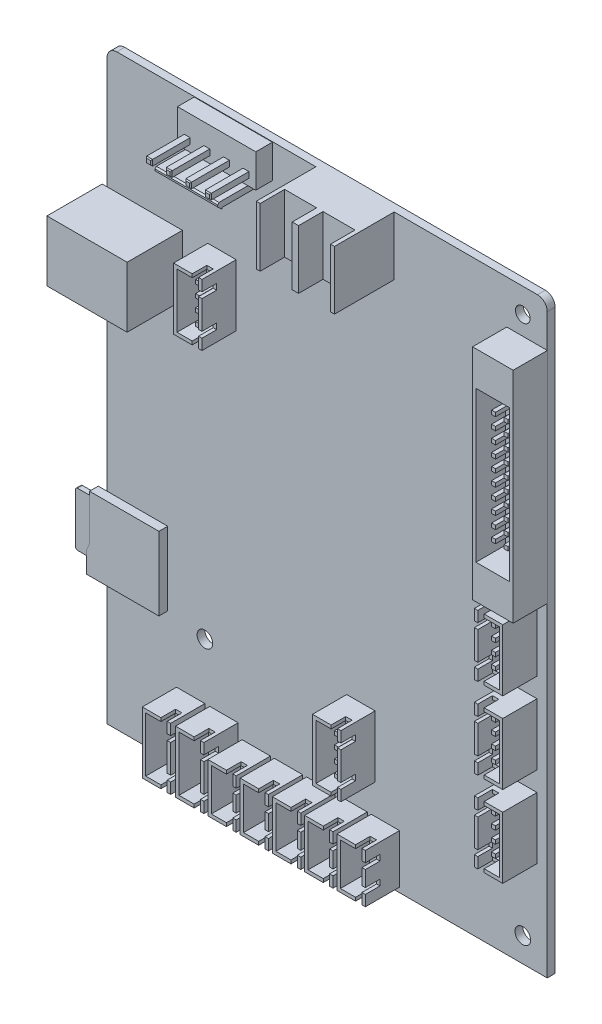
SolidWorks part; units mm, degrees
ref_plane "前视基准面" through (0, 0, 0) normal (0, 0, 1) x (1, 0, 0)
ref_plane "上视基准面" through (0, 0, 0) normal (0, 1, 0) x (1, 0, 0)
ref_plane "右视基准面" through (0, 0, 0) normal (1, 0, 0) x (0, 0, -1)
sketch "草图1" plane through (0, 0, 0) normal (0, 0, 1) x (1, 0, 0)
  line L0 (0, 0) -> (0, 50000) construction
  line L1 (43, -55) -> (-43, -55)
  line L2 (45, -53) -> (45, 53)
  line L3 (43, 55) -> (-43, 55)
  line L4 (-45, -53) -> (-45, 53)
  line L5 (45, -55) -> (-45, 55) construction
  line L6 (45, 55) -> (-45, -55) construction
  line L7 (0, 0) -> (50000, 0) construction
  arc A0 (-43, -55) -> (-45, -53) centre (-43, -53) cw
  arc A1 (43, -55) -> (45, -53) centre (43, -53) ccw
  arc A2 (45, 53) -> (43, 55) centre (43, 53) ccw
  arc A3 (-43, 55) -> (-45, 53) centre (-43, 53) ccw
  circle A4 centre (-40, 50) radius 1.5 construction
  circle A5 centre (40, 50) radius 1.5
  circle A6 centre (40, -50) radius 1.5 construction
  circle A7 centre (-40, -50) radius 1.5 construction
  point P0 (0, 0)
  dimension "D3" = 2
  dimension "D4" = 3
  dimension "D5" = 5
  dimension "D6" = 5
  dimension "D1" = 90
  dimension "D2" = 110
extrude "凸台-拉伸1" add sketch "草图1" along normal blind 1.6
sketch "草图2" plane through (0, 0, 1.6) normal (0, 0, 1) x (1, 0, 0)
  line L0 (43, 55) -> (-43, 55) construction
  line L1 (-46, 30.1) -> (-29.6, 30.1)
  line L2 (-46, 30.1) -> (-46, 17.7)
  line L3 (-46, 17.7) -> (-29.6, 17.7)
  line L4 (-29.6, 30.1) -> (-29.6, 17.7)
  line L5 (-45, 53) -> (-45, -53) construction
  dimension "D1" = 24.9
  dimension "D2" = 12.4
  dimension "D3" = 1
  dimension "D4" = 16.4
extrude "凸台-拉伸2" add sketch "草图2" along normal blind 11.3
sketch "草图3" plane through (-46, 0, 0) normal (-1, 0, 0) x (0, 0, 1)
  line L0 (12.9, 23.9) -> (50012.9, 23.9) construction
  line L1 (12.9, 30.1) -> (12.9, 17.7) construction
  line L2 (3, 28.7) -> (3, 19.1)
  line L3 (3, 19.1) -> (9.9, 19.1)
  line L4 (9.9, 19.1) -> (11.5, 20.7)
  line L5 (11.5, 20.7) -> (11.5, 27.1)
  line L6 (11.5, 27.1) -> (9.9, 28.7)
  line L7 (9.9, 28.7) -> (3, 28.7)
  line L8 (12.9, 30.1) -> (1.6, 30.1) construction
  line L9 (1.6, 30.1) -> (1.6, 17.7) construction
  line L11 (5.4, 26.6) -> (8.4, 26.6)
  line L12 (5.4, 26.6) -> (5.4, 21.2)
  line L13 (5.4, 21.2) -> (8.4, 21.2)
  line L14 (8.4, 26.6) -> (8.4, 21.2)
  point P4 (12.9, 23.9)
  dimension "D1" = 1.4
  dimension "D2" = 1.4
  dimension "D3" = 1.4
  dimension "D4" = 1.6
  dimension "D5" = 45
  dimension "D6" = 3
  dimension "D7" = 5.4
  dimension "D8" = 2.4
extrude "切除-拉伸1" cut sketch "草图3" against normal blind 9
sketch "草图4" plane through (0, 0, 1.6) normal (0, 0, 1) x (1, 0, 0)
  line L0 (-32.6, -23.8) -> (-32.6, -38.8)
  line L1 (-32.6, -38.8) -> (-47.4, -38.8)
  line L2 (-47.4, -38.8) -> (-47.4, -34.5)
  line L3 (-47.4, -34.5) -> (-46.8, -33.1886)
  line L4 (-46.8, -33.1886) -> (-46.8, -23.8)
  line L5 (-46.8, -23.8) -> (-32.6, -23.8)
  line L6 (-43, -55) -> (43, -55) construction
  line L7 (-45, 17.7) -> (-45, -53) construction
  dimension "D1" = 15
  dimension "D2" = 16.2
  dimension "D3" = 14.8
  dimension "D4" = 2.4
  dimension "D5" = 14.2
  dimension "D6" = 4.3
extrude "凸台-拉伸3" add sketch "草图4" along normal blind 1.8
sketch "草图5" plane through (-46.8, 0, 0) normal (-1, 0, 0) x (0, 0, 1)
  line L0 (3.4, -23.8) -> (3.4, -33.1886) construction
  line L1 (3.3, -24.6) -> (2.3, -24.6)
  line L2 (3.3, -24.6) -> (3.3, -35.6)
  line L3 (3.3, -35.6) -> (2.3, -35.6)
  line L4 (2.3, -24.6) -> (2.3, -35.6)
  line L5 (3.4, -23.8) -> (1.6, -23.8) construction
  dimension "D1" = 0.1
  dimension "D2" = 0.8
  dimension "D3" = 1
  dimension "D4" = 11
extrude "凸台-拉伸4" add sketch "草图5" along normal blind 3
fillet "圆角1" radius 0.5 2 edges at (-49.8, -24.6, 2.8) (-49.8, -35.6, 2.8)
sketch "草图6" plane through (0, 0, 1.6) normal (0, 0, 1) x (1, 0, 0)
  line L0 (-43, -55) -> (43, -55) construction
  line L1 (-25, -51.4) -> (-30.8, -51.4)
  line L2 (-25, -51.4) -> (-25, -64)
  line L3 (-25, -64) -> (-30.8, -64)
  line L4 (-30.8, -51.4) -> (-30.8, -64)
  line L5 (-45, -38.8) -> (-45, -53) construction
  dimension "D1" = 5.8
  dimension "D2" = 12.6
  dimension "D3" = 9
  dimension "D4" = 14.2
extrude "凸台-拉伸5" add sketch "草图6" along normal blind 7
sketch "草图7" plane through (0, 0, 8.6) normal (0, 0, 1) x (1, 0, 0)
  line L0 (-25, -51.4) -> (-30.8, -51.4) construction
  line L1 (-30.1, -52.1) -> (-25.7, -52.1)
  line L2 (-30.1, -52.1) -> (-30.1, -63.3)
  line L3 (-30.1, -63.3) -> (-25.7, -63.3)
  line L4 (-25.7, -52.1) -> (-25.7, -63.3)
  line L5 (-30.8, -64) -> (-25, -64) construction
  line L6 (-30.8, -51.4) -> (-30.8, -64) construction
  line L7 (-25, -64) -> (-25, -51.4) construction
  dimension "D1" = 0.7
  dimension "D2" = 0.7
  dimension "D3" = 0.7
  dimension "D4" = 0.7
extrude "切除-拉伸2" cut sketch "草图7" against normal blind 6
sketch "草图8" plane through (0, 0, 8.6) normal (0, 0, 1) x (1, 0, 0)
  line L1 (-27, -51.4) -> (-25.7, -51.4)
  line L2 (-27, -51.4) -> (-27, -52.1)
  line L3 (-27, -52.1) -> (-25.7, -52.1)
  line L4 (-25.7, -51.4) -> (-25.7, -52.1)
  line L5 (-25.7, -52.1) -> (-30.1, -52.1) construction
  line L7 (-25, -61.8) -> (-25, -60.6)
  line L8 (-25.7, -60.6) -> (-25, -60.6)
  line L9 (-25.7, -61.8) -> (-25.7, -60.6)
  line L10 (-25.7, -61.8) -> (-25, -61.8)
  line L12 (-25.7, -63.3) -> (-25.7, -52.1) construction
  line L13 (-25.7, -53.6) -> (-25, -53.6)
  line L14 (-25.7, -53.6) -> (-25.7, -54.8)
  line L15 (-25.7, -54.8) -> (-25, -54.8)
  line L16 (-25, -53.6) -> (-25, -54.8)
  line L17 (-25, -55) -> (-25, -51.4) construction
  line L19 (-25.7, -64) -> (-25.7, -63.3)
  line L20 (-27, -63.3) -> (-25.7, -63.3)
  line L21 (-27, -64) -> (-27, -63.3)
  line L22 (-27, -64) -> (-25.7, -64)
  line L23 (-30.8, -57.7) -> (49969.2, -57.7) construction
  line L24 (-30.8, -51.4) -> (-30.8, -64) construction
  line L26 (-30.8, -51.4) -> (-30.8, -55) construction
  line L27 (-25, -51.4) -> (-30.8, -51.4) construction
  point P34 (-30.8, -57.7)
  dimension "D1" = 3.8
  dimension "D2" = 2.2
  dimension "D4" = 1.2
extrude "切除-拉伸3" cut sketch "草图8" against normal blind 3
sketch "草图9" plane through (0, 0, 2.6) normal (0, 0, 1) x (1, 0, 0)
  line L0 (-30.8, -53.2) -> (49969.2, -53.2) construction
  line L1 (-30.8, -51.4) -> (-30.8, -55) construction
  line L2 (-27, -45.785) -> (-27, 49954.215) construction
  line L3 (-25, -55) -> (-25, -51.4) construction
  line L4 (-27, -51.55) -> (-27, -52.35)
  line L5 (-27, -49.05) -> (-27.8, -49.05)
  line L6 (-27, -49.05) -> (-27, -49.85)
  line L7 (-27, -49.85) -> (-27.8, -49.85)
  line L8 (-27.8, -49.05) -> (-27.8, -49.85)
  line L9 (-27, -51.55) -> (-27.8, -51.55)
  line L10 (-27.8, -51.55) -> (-27.8, -52.35)
  line L11 (-27, -52.35) -> (-27.8, -52.35)
  line L12 (-27, -54.05) -> (-27, -54.85)
  line L13 (-27, -54.05) -> (-27.8, -54.05)
  line L14 (-27.8, -54.05) -> (-27.8, -54.85)
  line L15 (-27, -54.85) -> (-27.8, -54.85)
  line L16 (-27, -56.55) -> (-27, -57.35)
  line L17 (-27, -56.55) -> (-27.8, -56.55)
  line L18 (-27.8, -56.55) -> (-27.8, -57.35)
  line L19 (-27, -57.35) -> (-27.8, -57.35)
  line L20 (-27, -49.05) -> (-27, -51.55) construction
  point P4 (-30.8, -53.2)
  dimension "D1" = 2
  dimension "D2" = 0.8
  dimension "D3" = 0.8
  dimension "D5" = 2.5
  dimension "D4" = 4
extrude "凸台-拉伸6" [suppressed] add sketch "草图9" along normal blind 4.5 and the other way blind 4
pattern_linear "阵列(线性)1" count 2 spacing 6.8 along (1, 0, 0) of "凸台-拉伸5", "切除-拉伸2", "切除-拉伸3", "凸台-拉伸6"
sketch "草图11" plane through (33.8907, 27.4604, 1.6) normal (0, 0, 1) x (1, 0, 0)
  line L1 (-24.0907, -62.7604) -> (-29.8907, -62.7604)
  line L2 (-24.0907, -62.7604) -> (-24.0907, -75.3604)
  line L3 (-24.0907, -75.3604) -> (-29.8907, -75.3604)
  line L4 (-29.8907, -62.7604) -> (-29.8907, -75.3604)
  line L6 (11.1093, -80.4604) -> (11.1093, 25.5396) construction
  line L7 (-76.8907, -82.4604) -> (-64.6907, -82.4604) construction
  dimension "D1" = 5.8
  dimension "D2" = 12.6
  dimension "D3" = 41
  dimension "D4" = 7.1
extrude "凸台-拉伸7" add sketch "草图11" along normal blind 7
sketch "草图13" plane through (33.8907, 27.4604, 8.6) normal (0, 0, 1) x (1, 0, 0)
  line L0 (-24.0907, -62.7604) -> (-29.8907, -62.7604) construction
  line L1 (-29.1907, -63.4604) -> (-24.7907, -63.4604)
  line L2 (-29.1907, -63.4604) -> (-29.1907, -74.6604)
  line L3 (-29.1907, -74.6604) -> (-24.7907, -74.6604)
  line L4 (-24.7907, -63.4604) -> (-24.7907, -74.6604)
  line L5 (-29.8907, -75.3604) -> (-24.0907, -75.3604) construction
  line L6 (-29.8907, -62.7604) -> (-29.8907, -75.3604) construction
  line L7 (-24.0907, -75.3604) -> (-24.0907, -62.7604) construction
  dimension "D1" = 0.7
  dimension "D2" = 0.7
  dimension "D3" = 0.7
  dimension "D4" = 0.7
extrude "切除-拉伸4" cut sketch "草图13" against normal blind 6
sketch "草图15" plane through (33.8907, 27.4604, 8.6) normal (0, 0, 1) x (1, 0, 0)
  line L1 (-26.0907, -62.7604) -> (-24.7907, -62.7604)
  line L2 (-26.0907, -62.7604) -> (-26.0907, -63.4604)
  line L3 (-26.0907, -63.4604) -> (-24.7907, -63.4604)
  line L4 (-24.7907, -62.7604) -> (-24.7907, -63.4604)
  line L5 (-24.7907, -63.4604) -> (-29.1907, -63.4604) construction
  line L7 (-24.0907, -73.1604) -> (-24.0907, -71.9604)
  line L8 (-24.7907, -71.9604) -> (-24.0907, -71.9604)
  line L9 (-24.7907, -73.1604) -> (-24.7907, -71.9604)
  line L10 (-24.7907, -73.1604) -> (-24.0907, -73.1604)
  line L12 (-24.7907, -74.6604) -> (-24.7907, -63.4604) construction
  line L13 (-24.7907, -64.9604) -> (-24.0907, -64.9604)
  line L14 (-24.7907, -64.9604) -> (-24.7907, -66.1604)
  line L15 (-24.7907, -66.1604) -> (-24.0907, -66.1604)
  line L16 (-24.0907, -64.9604) -> (-24.0907, -66.1604)
  line L17 (-24.0907, -75.3604) -> (-24.0907, -62.7604) construction
  line L19 (-24.7907, -75.3604) -> (-24.7907, -74.6604)
  line L20 (-26.0907, -74.6604) -> (-24.7907, -74.6604)
  line L21 (-26.0907, -75.3604) -> (-26.0907, -74.6604)
  line L22 (-26.0907, -75.3604) -> (-24.7907, -75.3604)
  line L23 (-30.8, -69.0604) -> (49969.2, -69.0604) construction
  line L24 (-29.8907, -62.7604) -> (-29.8907, -75.3604) construction
  line L26 (-29.8907, -62.7604) -> (-29.8907, -75.3604) construction
  line L27 (-24.0907, -62.7604) -> (-29.8907, -62.7604) construction
  point P34 (-29.8907, -69.0604)
  dimension "D1" = 3.8
  dimension "D2" = 2.2
  dimension "D4" = 1.2
extrude "切除-拉伸5" cut sketch "草图15" against normal blind 3
sketch "草图17" plane through (33.8907, 27.4604, 2.6) normal (0, 0, 1) x (1, 0, 0)
  line L0 (-30.8, -69.0604) -> (49969.2, -69.0604) construction
  line L1 (-29.8907, -62.7604) -> (-29.8907, -75.3604) construction
  line L2 (-26.0907, -45.785) -> (-26.0907, 49954.215) construction
  line L3 (-24.0907, -75.3604) -> (-24.0907, -62.7604) construction
  line L4 (-26.0907, -67.4104) -> (-26.0907, -68.2104)
  line L5 (-26.0907, -64.9104) -> (-26.8907, -64.9104)
  line L6 (-26.0907, -64.9104) -> (-26.0907, -65.7104)
  line L7 (-26.0907, -65.7104) -> (-26.8907, -65.7104)
  line L8 (-26.8907, -64.9104) -> (-26.8907, -65.7104)
  line L9 (-26.0907, -67.4104) -> (-26.8907, -67.4104)
  line L10 (-26.8907, -67.4104) -> (-26.8907, -68.2104)
  line L11 (-26.0907, -68.2104) -> (-26.8907, -68.2104)
  line L12 (-26.0907, -69.9104) -> (-26.0907, -70.7104)
  line L13 (-26.0907, -69.9104) -> (-26.8907, -69.9104)
  line L14 (-26.8907, -69.9104) -> (-26.8907, -70.7104)
  line L15 (-26.0907, -70.7104) -> (-26.8907, -70.7104)
  line L16 (-26.0907, -72.4104) -> (-26.0907, -73.2104)
  line L17 (-26.0907, -72.4104) -> (-26.8907, -72.4104)
  line L18 (-26.8907, -72.4104) -> (-26.8907, -73.2104)
  line L19 (-26.0907, -73.2104) -> (-26.8907, -73.2104)
  line L20 (-26.0907, -64.9104) -> (-26.0907, -67.4104) construction
  point P4 (-29.8907, -69.0604)
  dimension "D1" = 2
  dimension "D2" = 0.8
  dimension "D3" = 0.8
  dimension "D5" = 2.5
  dimension "D4" = 4
extrude "凸台-拉伸8" add sketch "草图17" along normal blind 4.5 and the other way blind 4
sketch "草图19" plane through (2.8423, 77.8774, 1.6) normal (0, 0, 1) x (1, 0, 0)
  line L0 (40.1577, -22.8774) -> (-45.8423, -22.8774) construction
  line L1 (-21.4423, -47.4774) -> (-27.2423, -47.4774)
  line L2 (-21.4423, -47.4774) -> (-21.4423, -60.0774)
  line L3 (-21.4423, -60.0774) -> (-27.2423, -60.0774)
  line L4 (-27.2423, -47.4774) -> (-27.2423, -60.0774)
  line L5 (-47.8423, -60.1774) -> (-47.8423, -101.6774) construction
  dimension "D1" = 5.8
  dimension "D2" = 12.6
  dimension "D3" = 24.6
  dimension "D4" = 20.6
extrude "凸台-拉伸9" add sketch "草图19" along normal blind 7
sketch "草图21" plane through (2.8423, 77.8774, 8.6) normal (0, 0, 1) x (1, 0, 0)
  line L0 (-21.4423, -47.4774) -> (-27.2423, -47.4774) construction
  line L1 (-26.5423, -48.1774) -> (-22.1423, -48.1774)
  line L2 (-26.5423, -48.1774) -> (-26.5423, -59.3774)
  line L3 (-26.5423, -59.3774) -> (-22.1423, -59.3774)
  line L4 (-22.1423, -48.1774) -> (-22.1423, -59.3774)
  line L5 (-27.2423, -60.0774) -> (-21.4423, -60.0774) construction
  line L6 (-27.2423, -47.4774) -> (-27.2423, -60.0774) construction
  line L7 (-21.4423, -60.0774) -> (-21.4423, -47.4774) construction
  dimension "D1" = 0.7
  dimension "D2" = 0.7
  dimension "D3" = 0.7
  dimension "D4" = 0.7
extrude "切除-拉伸6" cut sketch "草图21" against normal blind 6
sketch "草图23" plane through (2.8423, 77.8774, 8.6) normal (0, 0, 1) x (1, 0, 0)
  line L1 (-23.4423, -47.4774) -> (-22.1423, -47.4774)
  line L2 (-23.4423, -47.4774) -> (-23.4423, -48.1774)
  line L3 (-23.4423, -48.1774) -> (-22.1423, -48.1774)
  line L4 (-22.1423, -47.4774) -> (-22.1423, -48.1774)
  line L5 (-22.1423, -48.1774) -> (-26.5423, -48.1774) construction
  line L7 (-21.4423, -57.8774) -> (-21.4423, -56.6774)
  line L8 (-22.1423, -56.6774) -> (-21.4423, -56.6774)
  line L9 (-22.1423, -57.8774) -> (-22.1423, -56.6774)
  line L10 (-22.1423, -57.8774) -> (-21.4423, -57.8774)
  line L12 (-22.1423, -59.3774) -> (-22.1423, -48.1774) construction
  line L13 (-22.1423, -49.6774) -> (-21.4423, -49.6774)
  line L14 (-22.1423, -49.6774) -> (-22.1423, -50.8774)
  line L15 (-22.1423, -50.8774) -> (-21.4423, -50.8774)
  line L16 (-21.4423, -49.6774) -> (-21.4423, -50.8774)
  line L17 (-21.4423, -60.0774) -> (-21.4423, -47.4774) construction
  line L19 (-22.1423, -60.0774) -> (-22.1423, -59.3774)
  line L20 (-23.4423, -59.3774) -> (-22.1423, -59.3774)
  line L21 (-23.4423, -60.0774) -> (-23.4423, -59.3774)
  line L22 (-23.4423, -60.0774) -> (-22.1423, -60.0774)
  line L23 (-30.8, -53.7774) -> (49969.2, -53.7774) construction
  line L24 (-27.2423, -47.4774) -> (-27.2423, -60.0774) construction
  line L26 (-27.2423, -47.4774) -> (-27.2423, -60.0774) construction
  line L27 (-21.4423, -47.4774) -> (-27.2423, -47.4774) construction
  point P34 (-27.2423, -53.7774)
  dimension "D1" = 3.8
  dimension "D2" = 2.2
  dimension "D4" = 1.2
extrude "切除-拉伸7" cut sketch "草图23" against normal blind 3
sketch "草图25" plane through (2.8423, 77.8774, 2.6) normal (0, 0, 1) x (1, 0, 0)
  line L0 (-30.8, -53.7774) -> (49969.2, -53.7774) construction
  line L1 (-27.2423, -47.4774) -> (-27.2423, -60.0774) construction
  line L2 (-23.4423, -45.785) -> (-23.4423, 49954.215) construction
  line L3 (-21.4423, -60.0774) -> (-21.4423, -47.4774) construction
  line L4 (-23.4423, -52.1274) -> (-23.4423, -52.9274)
  line L5 (-23.4423, -49.6274) -> (-24.2423, -49.6274)
  line L6 (-23.4423, -49.6274) -> (-23.4423, -50.4274)
  line L7 (-23.4423, -50.4274) -> (-24.2423, -50.4274)
  line L8 (-24.2423, -49.6274) -> (-24.2423, -50.4274)
  line L9 (-23.4423, -52.1274) -> (-24.2423, -52.1274)
  line L10 (-24.2423, -52.1274) -> (-24.2423, -52.9274)
  line L11 (-23.4423, -52.9274) -> (-24.2423, -52.9274)
  line L12 (-23.4423, -54.6274) -> (-23.4423, -55.4274)
  line L13 (-23.4423, -54.6274) -> (-24.2423, -54.6274)
  line L14 (-24.2423, -54.6274) -> (-24.2423, -55.4274)
  line L15 (-23.4423, -55.4274) -> (-24.2423, -55.4274)
  line L16 (-23.4423, -57.1274) -> (-23.4423, -57.9274)
  line L17 (-23.4423, -57.1274) -> (-24.2423, -57.1274)
  line L18 (-24.2423, -57.1274) -> (-24.2423, -57.9274)
  line L19 (-23.4423, -57.9274) -> (-24.2423, -57.9274)
  line L20 (-23.4423, -49.6274) -> (-23.4423, -52.1274) construction
  point P4 (-27.2423, -53.7774)
  dimension "D1" = 2
  dimension "D2" = 0.8
  dimension "D3" = 0.8
  dimension "D5" = 2.5
  dimension "D4" = 4
extrude "凸台-拉伸10" add sketch "草图25" along normal blind 4.5 and the other way blind 4
sketch "草图27" plane through (67.7702, 21.0857, 1.6) normal (0, 0, 1) x (1, 0, 0)
  line L0 (-22.7702, -74.0857) -> (-22.7702, 31.9143) construction
  line L1 (-30.6702, -66.8857) -> (-24.8702, -66.8857)
  line L2 (-30.6702, -66.8857) -> (-30.6702, -54.2857)
  line L3 (-30.6702, -54.2857) -> (-24.8702, -54.2857)
  line L4 (-24.8702, -66.8857) -> (-24.8702, -54.2857)
  line L5 (-110.7702, -76.0857) -> (-98.5702, -76.0857) construction
  dimension "D1" = 5.8
  dimension "D2" = 12.6
  dimension "D3" = 2.1
  dimension "D4" = 9.2
extrude "凸台-拉伸11" add sketch "草图27" along normal blind 7
sketch "草图29" plane through (67.7702, 21.0857, 8.6) normal (0, 0, 1) x (1, 0, 0)
  line L0 (-30.6702, -66.8857) -> (-24.8702, -66.8857) construction
  line L1 (-25.5702, -66.1857) -> (-29.9702, -66.1857)
  line L2 (-25.5702, -66.1857) -> (-25.5702, -54.9857)
  line L3 (-25.5702, -54.9857) -> (-29.9702, -54.9857)
  line L4 (-29.9702, -66.1857) -> (-29.9702, -54.9857)
  line L5 (-24.8702, -54.2857) -> (-30.6702, -54.2857) construction
  line L6 (-24.8702, -66.8857) -> (-24.8702, -54.2857) construction
  line L7 (-30.6702, -54.2857) -> (-30.6702, -66.8857) construction
  dimension "D1" = 0.7
  dimension "D2" = 0.7
  dimension "D3" = 0.7
  dimension "D4" = 0.7
extrude "切除-拉伸8" cut sketch "草图29" against normal blind 6
sketch "草图31" plane through (67.7702, 21.0857, 8.6) normal (0, 0, 1) x (1, 0, 0)
  line L1 (-28.6702, -66.8857) -> (-29.9702, -66.8857)
  line L2 (-28.6702, -66.8857) -> (-28.6702, -66.1857)
  line L3 (-28.6702, -66.1857) -> (-29.9702, -66.1857)
  line L4 (-29.9702, -66.8857) -> (-29.9702, -66.1857)
  line L5 (-29.9702, -66.1857) -> (-25.5702, -66.1857) construction
  line L7 (-30.6702, -56.4857) -> (-30.6702, -57.6857)
  line L8 (-29.9702, -57.6857) -> (-30.6702, -57.6857)
  line L9 (-29.9702, -56.4857) -> (-29.9702, -57.6857)
  line L10 (-29.9702, -56.4857) -> (-30.6702, -56.4857)
  line L12 (-29.9702, -54.9857) -> (-29.9702, -66.1857) construction
  line L13 (-29.9702, -64.6857) -> (-30.6702, -64.6857)
  line L14 (-29.9702, -64.6857) -> (-29.9702, -63.4857)
  line L15 (-29.9702, -63.4857) -> (-30.6702, -63.4857)
  line L16 (-30.6702, -64.6857) -> (-30.6702, -63.4857)
  line L17 (-30.6702, -54.2857) -> (-30.6702, -66.8857) construction
  line L19 (-29.9702, -54.2857) -> (-29.9702, -54.9857)
  line L20 (-28.6702, -54.9857) -> (-29.9702, -54.9857)
  line L21 (-28.6702, -54.2857) -> (-28.6702, -54.9857)
  line L22 (-28.6702, -54.2857) -> (-29.9702, -54.2857)
  line L23 (-30.8, -60.5857) -> (49969.2, -60.5857) construction
  line L24 (-24.8702, -66.8857) -> (-24.8702, -54.2857) construction
  line L26 (-24.8702, -66.8857) -> (-24.8702, -54.2857) construction
  line L27 (-30.6702, -66.8857) -> (-24.8702, -66.8857) construction
  point P34 (-24.8702, -60.5857)
  dimension "D1" = 3.8
  dimension "D2" = 2.2
  dimension "D4" = 1.2
extrude "切除-拉伸9" cut sketch "草图31" against normal blind 3
sketch "草图33" plane through (67.7702, 21.0857, 2.6) normal (0, 0, 1) x (1, 0, 0)
  line L0 (-30.8, -60.5857) -> (49969.2, -60.5857) construction
  line L1 (-24.8702, -66.8857) -> (-24.8702, -54.2857) construction
  line L2 (-27.8702, -45.785) -> (-27.8702, 49954.215) construction
  line L3 (-30.6702, -54.2857) -> (-30.6702, -66.8857) construction
  line L4 (-27.8702, -58.9357) -> (-27.8702, -59.7357)
  line L5 (-27.8702, -56.4357) -> (-28.6702, -56.4357)
  line L6 (-27.8702, -56.4357) -> (-27.8702, -57.2357)
  line L7 (-27.8702, -57.2357) -> (-28.6702, -57.2357)
  line L8 (-28.6702, -56.4357) -> (-28.6702, -57.2357)
  line L9 (-27.8702, -58.9357) -> (-28.6702, -58.9357)
  line L10 (-28.6702, -58.9357) -> (-28.6702, -59.7357)
  line L11 (-27.8702, -59.7357) -> (-28.6702, -59.7357)
  line L12 (-27.8702, -61.4357) -> (-27.8702, -62.2357)
  line L13 (-27.8702, -61.4357) -> (-28.6702, -61.4357)
  line L14 (-28.6702, -61.4357) -> (-28.6702, -62.2357)
  line L15 (-27.8702, -62.2357) -> (-28.6702, -62.2357)
  line L16 (-27.8702, -63.9357) -> (-27.8702, -64.7357)
  line L17 (-27.8702, -63.9357) -> (-28.6702, -63.9357)
  line L18 (-28.6702, -63.9357) -> (-28.6702, -64.7357)
  line L19 (-27.8702, -64.7357) -> (-28.6702, -64.7357)
  line L20 (-27.8702, -56.4357) -> (-27.8702, -58.9357) construction
  point P4 (-24.8702, -60.5857)
  dimension "D1" = 2.8
  dimension "D2" = 0.8
  dimension "D3" = 0.8
  dimension "D5" = 2.5
  dimension "D4" = 4
extrude "凸台-拉伸12" add sketch "草图33" along normal blind 4.5 and the other way blind 4
pattern_linear "阵列(线性)2" count 3 spacing 16.6 along (0, 1, 0) of "凸台-拉伸11", "切除-拉伸8", "切除-拉伸9", "凸台-拉伸12"
sketch "草图35" plane through (13.4499, -1.0229, 1.6) normal (0, 0, 1) x (1, 0, 0)
  line L1 (-25.0499, -52.9771) -> (-30.8499, -52.9771)
  line L2 (-25.0499, -52.9771) -> (-25.0499, -62.9771)
  line L3 (-25.0499, -62.9771) -> (-30.8499, -62.9771)
  line L4 (-30.8499, -52.9771) -> (-30.8499, -62.9771)
  line L6 (-56.4499, -53.9771) -> (-44.2499, -53.9771) construction
  line L7 (-58.4499, -37.7771) -> (-58.4499, -51.9771) construction
  dimension "D1" = 5.8
  dimension "D2" = 10
  dimension "D3" = 9
  dimension "D4" = 27.6
extrude "凸台-拉伸13" add sketch "草图35" along normal blind 7
sketch "草图37" plane through (13.4499, -1.0229, 8.6) normal (0, 0, 1) x (1, 0, 0)
  line L0 (-25.0499, -52.9771) -> (-30.8499, -52.9771) construction
  line L1 (-30.1499, -53.6771) -> (-25.7499, -53.6771)
  line L2 (-30.1499, -53.6771) -> (-30.1499, -62.2771)
  line L3 (-30.1499, -62.2771) -> (-25.7499, -62.2771)
  line L4 (-25.7499, -53.6771) -> (-25.7499, -62.2771)
  line L5 (-30.8499, -62.9771) -> (-25.0499, -62.9771) construction
  line L6 (-30.8499, -52.9771) -> (-30.8499, -62.9771) construction
  line L7 (-25.0499, -62.9771) -> (-25.0499, -52.9771) construction
  dimension "D1" = 0.7
  dimension "D2" = 0.7
  dimension "D3" = 0.7
  dimension "D4" = 0.7
extrude "切除-拉伸10" cut sketch "草图37" against normal blind 6
sketch "草图39" plane through (13.4499, -1.0229, 8.6) normal (0, 0, 1) x (1, 0, 0)
  line L1 (-27.0499, -52.9771) -> (-25.7499, -52.9771)
  line L2 (-27.0499, -52.9771) -> (-27.0499, -53.6771)
  line L3 (-27.0499, -53.6771) -> (-25.7499, -53.6771)
  line L4 (-25.7499, -52.9771) -> (-25.7499, -53.6771)
  line L5 (-25.7499, -53.6771) -> (-30.1499, -53.6771) construction
  line L7 (-25.0499, -60.7771) -> (-25.0499, -59.5771)
  line L8 (-25.7499, -59.5771) -> (-25.0499, -59.5771)
  line L9 (-25.7499, -60.7771) -> (-25.7499, -59.5771)
  line L10 (-25.7499, -60.7771) -> (-25.0499, -60.7771)
  line L12 (-25.7499, -62.2771) -> (-25.7499, -53.6771) construction
  line L13 (-25.7499, -55.1771) -> (-25.0499, -55.1771)
  line L14 (-25.7499, -55.1771) -> (-25.7499, -56.3771)
  line L15 (-25.7499, -56.3771) -> (-25.0499, -56.3771)
  line L16 (-25.0499, -55.1771) -> (-25.0499, -56.3771)
  line L17 (-25.0499, -53.9771) -> (-25.0499, -52.9771) construction
  line L19 (-25.7499, -62.9771) -> (-25.7499, -62.2771)
  line L20 (-27.0499, -62.2771) -> (-25.7499, -62.2771)
  line L21 (-27.0499, -62.9771) -> (-27.0499, -62.2771)
  line L22 (-27.0499, -62.9771) -> (-25.7499, -62.9771)
  line L23 (-30.8, -57.9771) -> (49969.2, -57.9771) construction
  line L24 (-30.8499, -52.9771) -> (-30.8499, -62.9771) construction
  line L26 (-30.8499, -52.9771) -> (-30.8499, -53.9771) construction
  line L27 (-25.0499, -52.9771) -> (-30.8499, -52.9771) construction
  point P34 (-30.8499, -57.9771)
  dimension "D1" = 3.8
  dimension "D2" = 2.2
  dimension "D4" = 1.2
extrude "切除-拉伸11" cut sketch "草图39" against normal blind 3
sketch "草图41" plane through (13.4499, -1.0229, 2.6) normal (0, 0, 1) x (1, 0, 0)
  line L0 (-30.8, -53.4771) -> (49969.2, -53.4771) construction
  line L1 (-30.8499, -52.9771) -> (-30.8499, -53.9771) construction
  line L2 (-27.0499, -45.785) -> (-27.0499, 49954.215) construction
  line L3 (-25.0499, -53.9771) -> (-25.0499, -52.9771) construction
  line L4 (-27.0499, -53.0771) -> (-27.0499, -53.8771)
  line L5 (-27.0499, -50.5771) -> (-27.8499, -50.5771)
  line L6 (-27.0499, -50.5771) -> (-27.0499, -51.3771)
  line L7 (-27.0499, -51.3771) -> (-27.8499, -51.3771)
  line L8 (-27.8499, -50.5771) -> (-27.8499, -51.3771)
  line L9 (-27.0499, -53.0771) -> (-27.8499, -53.0771)
  line L10 (-27.8499, -53.0771) -> (-27.8499, -53.8771)
  line L11 (-27.0499, -53.8771) -> (-27.8499, -53.8771)
  line L12 (-27.0499, -55.5771) -> (-27.0499, -56.3771)
  line L13 (-27.0499, -55.5771) -> (-27.8499, -55.5771)
  line L14 (-27.8499, -55.5771) -> (-27.8499, -56.3771)
  line L15 (-27.0499, -56.3771) -> (-27.8499, -56.3771)
  line L20 (-27.0499, -50.5771) -> (-27.0499, -53.0771) construction
  line L21 (-27.0499, -58.0771) -> (-27.0499, -58.8771) [skipped]
  line L22 (-27.0499, -58.0771) -> (-27.8499, -58.0771) [skipped]
  line L23 (-27.8499, -58.0771) -> (-27.8499, -58.8771) [skipped]
  line L24 (-27.0499, -58.8771) -> (-27.8499, -58.8771) [skipped]
  point P4 (-30.8499, -53.4771)
  dimension "D1" = 2
  dimension "D2" = 0.8
  dimension "D3" = 0.8
  dimension "D5" = 2.5
  dimension "D4" = 4
extrude "凸台-拉伸14" [suppressed] add sketch "草图41" along normal blind 4.5 and the other way blind 4
pattern_linear "阵列(线性)3" count 5 spacing 6.6 along (1, 0, 0) of "凸台-拉伸13", "切除-拉伸10", "切除-拉伸11", "凸台-拉伸14"
sketch "草图43" plane through (66.8909, 85.5626, 1.6) normal (0, 0, 1) x (1, 0, 0)
  line L1 (-30.1665, -84.2273) -> (-21.8665, -84.2273)
  line L2 (-30.1665, -84.2273) -> (-30.1665, -39.4273)
  line L3 (-30.1665, -39.4273) -> (-21.8665, -39.4273)
  line L4 (-21.8665, -84.2273) -> (-21.8665, -39.4273)
  dimension "D1" = 8.3
  dimension "D2" = 44.8
extrude "凸台-拉伸15" add sketch "草图43" along normal blind 7
sketch "草图45" plane through (66.8909, 85.5626, 8.6) normal (0, 0, 1) x (1, 0, 0)
  line L0 (-30.1665, -84.2273) -> (-21.8665, -84.2273) construction
  line L1 (-22.5665, -77.2273) -> (-29.4665, -77.2273)
  line L2 (-22.5665, -77.2273) -> (-22.5665, -46.4273)
  line L3 (-22.5665, -46.4273) -> (-29.4665, -46.4273)
  line L4 (-29.4665, -77.2273) -> (-29.4665, -46.4273)
  line L5 (-21.8665, -39.4273) -> (-30.1665, -39.4273) construction
  line L6 (-21.8665, -84.2273) -> (-21.8665, -39.4273) construction
  line L7 (-30.1665, -39.4273) -> (-30.1665, -84.2273) construction
  dimension "D1" = 7
  dimension "D2" = 7
  dimension "D3" = 0.7
  dimension "D4" = 0.7
extrude "切除-拉伸12" cut sketch "草图45" against normal blind 6
sketch "草图49" plane through (66.8909, 85.5626, 2.6) normal (0, 0, 1) x (1, 0, 0)
  line L0 (-30.8, -61.8273) -> (49969.2, -61.8273) construction
  line L1 (-21.8665, -84.2273) -> (-21.8665, -39.4273) construction
  line L2 (-26.9665, -45.785) -> (-26.9665, 49954.215) construction
  line L3 (-30.1665, -39.4273) -> (-30.1665, -84.2273) construction
  line L4 (-26.9665, -52.6773) -> (-26.9665, -53.4773)
  line L5 (-26.9665, -50.1773) -> (-27.7665, -50.1773)
  line L6 (-26.9665, -50.1773) -> (-26.9665, -50.9773)
  line L7 (-26.9665, -50.9773) -> (-27.7665, -50.9773)
  line L8 (-27.7665, -50.1773) -> (-27.7665, -50.9773)
  line L9 (-26.9665, -52.6773) -> (-27.7665, -52.6773)
  line L10 (-27.7665, -52.6773) -> (-27.7665, -53.4773)
  line L11 (-26.9665, -53.4773) -> (-27.7665, -53.4773)
  line L12 (-26.9665, -55.1773) -> (-26.9665, -55.9773)
  line L13 (-26.9665, -55.1773) -> (-27.7665, -55.1773)
  line L14 (-27.7665, -55.1773) -> (-27.7665, -55.9773)
  line L15 (-26.9665, -55.9773) -> (-27.7665, -55.9773)
  line L16 (-26.9665, -57.6773) -> (-26.9665, -58.4773)
  line L17 (-26.9665, -57.6773) -> (-27.7665, -57.6773)
  line L18 (-27.7665, -57.6773) -> (-27.7665, -58.4773)
  line L19 (-26.9665, -58.4773) -> (-27.7665, -58.4773)
  line L20 (-26.9665, -50.1773) -> (-26.9665, -52.6773) construction
  line L21 (-26.9665, -60.1773) -> (-26.9665, -60.9773)
  line L22 (-26.9665, -60.1773) -> (-27.7665, -60.1773)
  line L23 (-27.7665, -60.1773) -> (-27.7665, -60.9773)
  line L24 (-26.9665, -60.9773) -> (-27.7665, -60.9773)
  line L25 (-26.9665, -62.6773) -> (-26.9665, -63.4773)
  line L26 (-26.9665, -62.6773) -> (-27.7665, -62.6773)
  line L27 (-27.7665, -62.6773) -> (-27.7665, -63.4773)
  line L28 (-26.9665, -63.4773) -> (-27.7665, -63.4773)
  line L29 (-26.9665, -65.1773) -> (-26.9665, -65.9773)
  line L30 (-26.9665, -65.1773) -> (-27.7665, -65.1773)
  line L31 (-27.7665, -65.1773) -> (-27.7665, -65.9773)
  line L32 (-26.9665, -65.9773) -> (-27.7665, -65.9773)
  line L33 (-26.9665, -67.6773) -> (-26.9665, -68.4773)
  line L34 (-26.9665, -67.6773) -> (-27.7665, -67.6773)
  line L35 (-27.7665, -67.6773) -> (-27.7665, -68.4773)
  line L36 (-26.9665, -68.4773) -> (-27.7665, -68.4773)
  line L37 (-26.9665, -70.1773) -> (-26.9665, -70.9773)
  line L38 (-26.9665, -70.1773) -> (-27.7665, -70.1773)
  line L39 (-27.7665, -70.1773) -> (-27.7665, -70.9773)
  line L40 (-26.9665, -70.9773) -> (-27.7665, -70.9773)
  line L41 (-26.9665, -72.6773) -> (-26.9665, -73.4773)
  line L42 (-26.9665, -72.6773) -> (-27.7665, -72.6773)
  line L43 (-27.7665, -72.6773) -> (-27.7665, -73.4773)
  line L44 (-26.9665, -73.4773) -> (-27.7665, -73.4773)
  line L45 (-24.4065, -52.6773) -> (-24.4065, -53.4773)
  line L46 (-24.4065, -50.1773) -> (-25.2065, -50.1773)
  line L47 (-24.4065, -50.1773) -> (-24.4065, -50.9773)
  line L48 (-24.4065, -50.9773) -> (-25.2065, -50.9773)
  line L49 (-25.2065, -50.1773) -> (-25.2065, -50.9773)
  line L50 (-24.4065, -52.6773) -> (-25.2065, -52.6773)
  line L51 (-25.2065, -52.6773) -> (-25.2065, -53.4773)
  line L52 (-24.4065, -53.4773) -> (-25.2065, -53.4773)
  line L53 (-24.4065, -55.1773) -> (-24.4065, -55.9773)
  line L54 (-24.4065, -55.1773) -> (-25.2065, -55.1773)
  line L55 (-25.2065, -55.1773) -> (-25.2065, -55.9773)
  line L56 (-24.4065, -55.9773) -> (-25.2065, -55.9773)
  line L57 (-24.4065, -57.6773) -> (-24.4065, -58.4773)
  line L58 (-24.4065, -57.6773) -> (-25.2065, -57.6773)
  line L59 (-25.2065, -57.6773) -> (-25.2065, -58.4773)
  line L60 (-24.4065, -58.4773) -> (-25.2065, -58.4773)
  line L61 (-24.4065, -60.1773) -> (-24.4065, -60.9773)
  line L62 (-24.4065, -60.1773) -> (-25.2065, -60.1773)
  line L63 (-25.2065, -60.1773) -> (-25.2065, -60.9773)
  line L64 (-24.4065, -60.9773) -> (-25.2065, -60.9773)
  line L65 (-24.4065, -62.6773) -> (-24.4065, -63.4773)
  line L66 (-24.4065, -62.6773) -> (-25.2065, -62.6773)
  line L67 (-25.2065, -62.6773) -> (-25.2065, -63.4773)
  line L68 (-24.4065, -63.4773) -> (-25.2065, -63.4773)
  line L69 (-24.4065, -65.1773) -> (-24.4065, -65.9773)
  line L70 (-24.4065, -65.1773) -> (-25.2065, -65.1773)
  line L71 (-25.2065, -65.1773) -> (-25.2065, -65.9773)
  line L72 (-24.4065, -65.9773) -> (-25.2065, -65.9773)
  line L73 (-24.4065, -67.6773) -> (-24.4065, -68.4773)
  line L74 (-24.4065, -67.6773) -> (-25.2065, -67.6773)
  line L75 (-25.2065, -67.6773) -> (-25.2065, -68.4773)
  line L76 (-24.4065, -68.4773) -> (-25.2065, -68.4773)
  line L77 (-24.4065, -70.1773) -> (-24.4065, -70.9773)
  line L78 (-24.4065, -70.1773) -> (-25.2065, -70.1773)
  line L79 (-25.2065, -70.1773) -> (-25.2065, -70.9773)
  line L80 (-24.4065, -70.9773) -> (-25.2065, -70.9773)
  line L81 (-24.4065, -72.6773) -> (-24.4065, -73.4773)
  line L82 (-24.4065, -72.6773) -> (-25.2065, -72.6773)
  line L83 (-25.2065, -72.6773) -> (-25.2065, -73.4773)
  line L84 (-24.4065, -73.4773) -> (-25.2065, -73.4773)
  line L85 (-24.4065, -50.1773) -> (-24.4065, -52.6773) construction
  point P4 (-21.8665, -61.8273)
  dimension "D1" = 3.2
  dimension "D2" = 0.8
  dimension "D3" = 0.8
  dimension "D5" = 2.5
  dimension "D4" = 10
  dimension "D6" = 2
extrude "凸台-拉伸16" add sketch "草图49" along normal blind 4.5 and the other way blind 4
sketch "草图50" plane through (0, 0, 1.6) normal (0, 0, 1) x (1, 0, 0)
  line L0 (-27.2, 48.1) -> (-25.6, 48.1)
  line L1 (-27.2, 54.9) -> (-11.2, 54.9)
  line L2 (-27.2, 54.9) -> (-27.2, 48.1)
  line L3 (-25.6, 46.9) -> (-12.8, 46.9)
  line L4 (-11.2, 54.9) -> (-11.2, 48.1)
  line L5 (-25.6, 48.1) -> (-25.6, 46.9)
  line L6 (-11.2, 48.1) -> (-12.8, 48.1)
  line L7 (-12.8, 48.1) -> (-12.8, 46.9)
  line L8 (-19.2, 55.1892) -> (-19.2, 56.9888) construction
  line L9 (43, 55) -> (-43, 55) construction
  line L10 (-45, 53) -> (-45, 30.1) construction
  dimension "D1" = 16
  dimension "D2" = 8
  dimension "D3" = 0.1
  dimension "D4" = 17.8
  dimension "D5" = 12.8
  dimension "D6" = 1.2
extrude "凸台-拉伸17" add sketch "草图50" along normal blind 3.4
sketch "草图51" plane through (-25.6, 0, 0) normal (-1, 0, 0) x (0, 0, 1)
  line L0 (5, 48.1) -> (10.9196, 48.1)
  line L1 (10.9196, 48.1) -> (11.2, 47.7757)
  line L2 (11.2, 47.7757) -> (11.2, 47.4328)
  line L3 (11.2, 47.4328) -> (10.306, 46.5883)
  line L4 (10.306, 46.5883) -> (10.306, 46.9)
  line L5 (10.306, 46.9) -> (5, 46.9)
  line L6 (5, 54.9) -> (5, 48.1) construction
  line L7 (5, 46.9) -> (5, 48.1)
  dimension "D1" = 6.2
extrude "凸台-拉伸18" add sketch "草图51" against normal up to surface (12.8 mm away) up to face at (-12.8, 47.5, 3.3)
sketch "草图52" plane through (0, 0, 5) normal (0, 0, 1) x (1, 0, 0)
  line L0 (-17.8, 49.5) -> (-16.6, 49.5)
  line L1 (-13.8, 49.5) -> (-12.6, 49.5)
  line L2 (-13.8, 49.5) -> (-13.8, 50.7)
  line L3 (-13.8, 50.7) -> (-12.6, 50.7)
  line L4 (-12.6, 49.5) -> (-12.6, 50.7)
  line L5 (-17.8, 49.5) -> (-17.8, 50.7)
  line L6 (-17.8, 50.7) -> (-16.6, 50.7)
  line L7 (-16.6, 49.5) -> (-16.6, 50.7)
  line L8 (-21.8, 49.5) -> (-20.6, 49.5)
  line L9 (-21.8, 49.5) -> (-21.8, 50.7)
  line L10 (-21.8, 50.7) -> (-20.6, 50.7)
  line L11 (-20.6, 49.5) -> (-20.6, 50.7)
  line L12 (-25.8, 49.5) -> (-24.6, 49.5)
  line L13 (-25.8, 49.5) -> (-25.8, 50.7)
  line L14 (-25.8, 50.7) -> (-24.6, 50.7)
  line L15 (-24.6, 49.5) -> (-24.6, 50.7)
  line L16 (-19.2, 54.9) -> (-19.2, 50054.9) construction
  line L17 (-11.2, 54.9) -> (-27.2, 54.9) construction
  line L18 (-11.2, 54.9) -> (-27.2, 54.9) construction
  point P20 (-19.2, 54.9)
  dimension "D1" = 1.2
  dimension "D2" = 1.2
  dimension "D4" = 4.2
  dimension "D3" = 4
extrude "凸台-拉伸19" add sketch "草图52" along normal blind 7.9 and the other way blind 6
chamfer "倒角1" distance 0.2 angle 45 16 edges at (-13.2, 50.7, 12.9) (-12.6, 50.1, 12.9) (-13.2, 49.5, 12.9) (-13.8, 50.1, 12.9) (-17.2, 50.7, 12.9) (-16.6, 50.1, 12.9) (-17.2, 49.5, 12.9) (-17.8, 50.1, 12.9) (-21.2, 50.7, 12.9) (-20.6, 50.1, 12.9) (-21.2, 49.5, 12.9) (-21.8, 50.1, 12.9) (-25.2, 50.7, 12.9) (-24.6, 50.1, 12.9) (-25.2, 49.5, 12.9) (-25.8, 50.1, 12.9)
sketch "草图53" plane through (0, 0, 1.6) normal (0, 0, 1) x (1, 0, 0)
  line L0 (43, 55) -> (-43, 55) construction
  line L1 (-2.3, 55) -> (13.7, 55)
  line L2 (-2.3, 55) -> (-2.3, 43)
  line L3 (-2.3, 43) -> (13.7, 43)
  line L4 (13.7, 55) -> (13.7, 43)
  line L5 (-45, 53) -> (-45, 30.1) construction
  dimension "D1" = 12
  dimension "D2" = 16
  dimension "D3" = 42.7
extrude "凸台-拉伸20" add sketch "草图53" along normal blind 12.2
sketch "草图54" plane through (0, 0, 13.8) normal (0, 0, 1) x (1, 0, 0)
  line L0 (13.7, 55) -> (-2.3, 55) construction
  line L1 (-1.5, 55) -> (5.05, 55)
  line L2 (-1.5, 55) -> (-1.5, 43)
  line L3 (-1.5, 43) -> (5.05, 43)
  line L4 (5.05, 55) -> (5.05, 43)
  line L5 (-2.3, 43) -> (13.7, 43) construction
  line L6 (-2.3, 43) -> (13.7, 43) construction
  line L7 (12.9, 55) -> (6.35, 55)
  line L8 (12.9, 55) -> (12.9, 43)
  line L9 (12.9, 43) -> (6.35, 43)
  line L10 (6.35, 55) -> (6.35, 43)
  line L11 (13.7, 43) -> (13.7, 55) construction
  line L12 (-2.3, 55) -> (-2.3, 43) construction
  line L13 (5.7, 55) -> (5.7, 50055) construction
  point P20 (5.7, 55)
  dimension "D1" = 0.8
  dimension "D2" = 0.8
  dimension "D3" = 1.3
extrude "切除-拉伸14" cut sketch "草图54" against normal blind 5
sketch "草图55" [suppressed] plane through (0, 0, 8.8) normal (0, 0, 1) x (1, 0, 0)
  line L0 (5.7, 55) -> (5.7, 50055) construction
  line L1 (-0.919, 54.0541) -> (4.3354, 54.0541)
  line L2 (-0.919, 54.0541) -> (-0.919, 44.0732)
  line L3 (-0.919, 44.0732) -> (4.3354, 44.0732)
  line L4 (4.3354, 54.0541) -> (4.3354, 44.0732)
  line L5 (6.35, 55) -> (5.05, 55) construction
  line L6 (7.0646, 54.0541) -> (7.0646, 44.0732)
  line L7 (12.319, 44.0732) -> (7.0646, 44.0732)
  line L8 (12.319, 54.0541) -> (12.319, 44.0732)
  line L9 (12.319, 54.0541) -> (7.0646, 54.0541)
  point P8 (5.7, 55)
extrude "凸台-拉伸21" [suppressed] add sketch "草图55" along normal blind 1
sketch "草图56" [suppressed] plane through (0, 0, 9.8) normal (0, 0, 1) x (1, 0, 0)
  line L0 (5.7, 55) -> (5.7, 50055) construction
  line L1 (6.35, 55) -> (5.05, 55) construction
  circle A0 centre (1.6821, 49.0636) radius 2.0879
  circle A1 centre (9.7179, 49.0636) radius 2.0879
  point P6 (5.7, 55)
extrude "凸台-拉伸22" [suppressed] add sketch "草图56" along normal blind 2
fillet "圆角2" [suppressed] radius 1
sketch "草图57" plane through (0, -55, 0) normal (0, -1, 0) x (1, 0, 0)
  line L0 (45, 1.6) -> (45, 0)
  line L1 (45, 0) -> (-45, 0)
  line L2 (-45, 0) -> (-45, 1.6)
  line L3 (-45, 1.6) -> (45, 1.6)
extrude "凸台-拉伸23" add sketch "草图57" along normal blind 10
sketch "草图58" plane through (0, 0, 1.6) normal (0, 0, 1) x (1, 0, 0)
  line L0 (45, -65) -> (-45, -65) construction
  line L1 (45, -65) -> (45, -55) construction
  circle A0 centre (-40, -60) radius 1.6 construction
  circle A1 centre (40, -60) radius 1.6
  circle A3 centre (40, 50) radius 1.5 construction
  dimension "D1" = 5
  dimension "D2" = 3.2
  dimension "D3" = 110
  dimension "D4" = 3.2
  dimension "D5" = 5
extrude "切除-拉伸15" cut sketch "草图58" against normal blind 10
sketch "草图59" plane through (0, 0, 1.6) normal (0, 0, 1) x (1, 0, 0)
  line L0 (-45, 53) -> (-45, 30.1) construction
  line L2 (45, -65) -> (-45, -65) construction
  line L3 (-45, 17.7) -> (-45, -23.8) construction
  circle A0 centre (-25, -40) radius 1.6
  circle A1 centre (-25, 40) radius 1.6
  dimension "D1" = 20
  dimension "D2" = 80
  dimension "D3" = 25
  dimension "D4" = 20
extrude "切除-拉伸16" cut sketch "草图59" against normal blind 10
sketch "草图60" plane through (0, 0, 1.6) normal (0, 0, 1) x (1, 0, 0)
  line L0 (-45, -53) -> (-45, -55)
  line L1 (-45, -55) -> (-43, -55)
  line L2 (-43, -55) -> (-43, -53)
  line L3 (-43, -53) -> (-45, -53)
  line L4 (45, -55) -> (45, -51.4629)
  line L5 (45, -53) -> (45, 1.3353) construction
  line L6 (45, -51.4629) -> (42.3242, -51.4629)
  line L7 (42.3242, -51.4629) -> (42.3242, -55)
  line L8 (42.3242, -55) -> (45, -55)
extrude "凸台-拉伸24" add sketch "草图60" against normal blind 1.6
